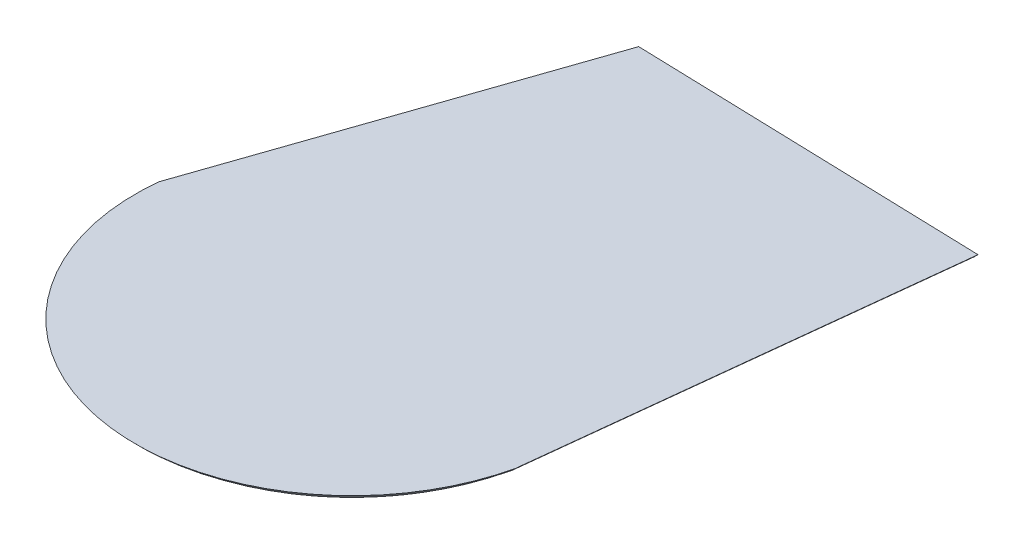
SolidWorks part; units mm, degrees
ref_plane "Front Plane" through (0, 0, 0) normal (0, 0, 1) x (1, 0, 0)
ref_plane "Top Plane" through (0, 0, 0) normal (0, 1, 0) x (1, 0, 0)
ref_plane "Right Plane" through (0, 0, 0) normal (1, 0, 0) x (0, 0, -1)
sketch "Sketch1" plane through (0, 0, 0) normal (0, 1, 0) x (1, 0, 0)
  line L0 (0.5967, 22.5443) -> (-43.0392, 23.8579)
  line L1 (-43.0392, 23.8579) -> (-58.3617, -20.6716)
  line L2 (-5.1614, -29.3679) -> (-3.6085, -15.3679)
  line L3 (-3.6085, -15.3679) -> (-16.7288, -12.421)
  line L4 (-16.7288, -12.421) -> (-21.8267, -35.1183)
  line L5 (-21.8267, -35.1183) -> (-45.2433, -29.8588)
  line L6 (-45.2433, -29.8588) -> (-38.6114, -0.3317)
  line L7 (-38.6114, -0.3317) -> (-2.8321, -8.3679)
  line L8 (-2.8321, -8.3679) -> (0.5967, 22.5443)
  line L9 (0.5967, 22.5443) -> (-5.1614, -29.3679)
  arc A0 (-58.3617, -20.6716) -> (-5.1614, -29.3679) centre (-31.5051, -23.451) ccw
extrude "Boss-Extrude1" add sketch "Sketch1" along normal blind 2 contours L1 A0 L2 L3 L4 L5 L6 L7 L8 L0 | L9 L7 L6 L5 L4 L3 region at (-2.0614, 0, -7.1929) region at (-27.9137, 0, 16.9141)
fillet "Fillet1" radius 6 3 edges at (-50.7004, 2, -1.5931) (-35.8608, 2, 50.0974) (-2.2824, 2, 3.4118)
mirror "Mirror1" about plane through (0, 2, 0) normal (0, 1, 0) of bodies 101
delete or keep bodies "Body-Delete/Keep 1" type delete bodies bodies 101
